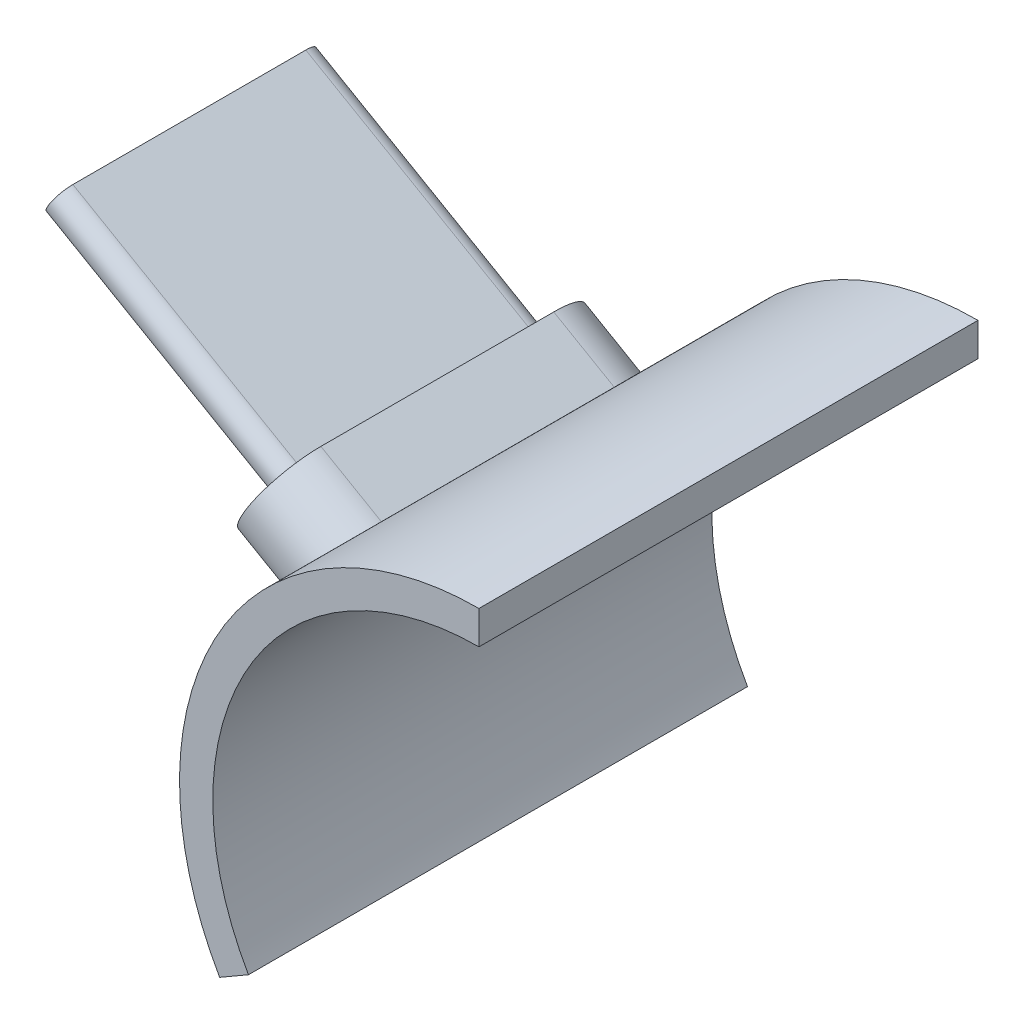
SolidWorks part; units mm, degrees
ref_plane "Plan de face" through (0, 0, 0) normal (0, 0, 1) x (1, 0, 0)
ref_plane "Plan de dessus" through (0, 0, 0) normal (0, 1, 0) x (1, 0, 0)
ref_plane "Plan de droite" through (0, 0, 0) normal (1, 0, 0) x (0, 0, -1)
sketch "Esquisse1" plane through (0, 0, 0) normal (0, 0, 1) x (1, 0, 0)
  line L0 (0, 9) -> (0, -9) construction
  line L1 (-7.7942, -4.5) -> (-6.9282, -4)
  line L3 (0, 9) -> (7.7942, -4.5) construction
  line L4 (7.7942, -4.5) -> (-7.7942, -4.5) construction
  line L5 (-7.7942, -4.5) -> (0, 9) construction
  line L6 (0, 9) -> (0, 8)
  arc A0 (0, 8) -> (-6.9282, -4) centre (0, 0) ccw
  arc A1 (0, 9) -> (-7.7942, -4.5) centre (0, 0) ccw
  circle A3 centre (0, 0) radius 8 construction
  circle A4 centre (0, 0) radius 9 construction
  point P1 (5, 0)
  point P7 (0, 8)
  point P8 (0, -8)
  point P11 (3.8252, 1.1695)
  dimension "D1" = 16
  dimension "D2" = 1
extrude "Boss.-Extru.1" add sketch "Esquisse1" against normal blind 15
ref_axis "Axe1" through (-6.9282, 4, 0) along (-0.866, 0.5, 0)
ref_plane "Plan1" through (-7.7942, 4.5, 0) normal (-0.866, 0.5, 0) x (0, 0, 1)
sketch "Esquisse2" plane through (-7.7942, 4.5, 0) normal (-0.866, 0.5, 0) x (0, 0, 1)
  line L0 (-11, 0) -> (-4, 0) construction
  line L1 (-11, 0.5) -> (-4, 0.5)
  line L2 (-11, -0.5) -> (-4, -0.5)
  line L3 (-7.5, 7.7942) -> (-7.5, -7.7942) construction
  line L6 (-15, -7.7942) -> (0, -7.7942) construction
  line L7 (-15, 7.7942) -> (0, 7.7942) construction
  arc A0 (-11, 0.5) -> (-11, -0.5) centre (-11, 0) ccw
  arc A1 (-4, -0.5) -> (-4, 0.5) centre (-4, 0) ccw
  point P3 (-7.5, 0)
  dimension "D1" = 7
  dimension "D2" = 1
extrude "Boss.-Extru.2" add sketch "Esquisse2" along normal blind 10 and the other way up to next (1 mm away)
ref_plane "Plan2" through (-8.0322, 4.06, -4) normal (0, 0, -1) x (-1, 0, 0)
sketch "Esquisse7" plane through (-7.7942, 4.5, 0) normal (-0.866, 0.5, 0) x (0, 0, 1)
  line L0 (-4, 1.55) -> (-11, 1.55) construction
  line L1 (-11, -1.55) -> (-4, -1.55) construction
  line L2 (-4, 1.55) -> (-11, 1.55)
  line L4 (-11, -1.55) -> (-4, -1.55)
  arc A0 (-4, -1.55) -> (-4, 1.55) centre (-4, 0) ccw construction
  arc A1 (-11, 1.55) -> (-11, -1.55) centre (-11, 0) ccw construction
  arc A2 (-4, -1.55) -> (-4, 1.55) centre (-4, 0) ccw
  arc A3 (-11, 1.55) -> (-11, -1.55) centre (-11, 0) ccw
extrude "Boss.-Extru.4" add sketch "Esquisse7" along normal blind 2 and the other way up to next (1 mm away)
